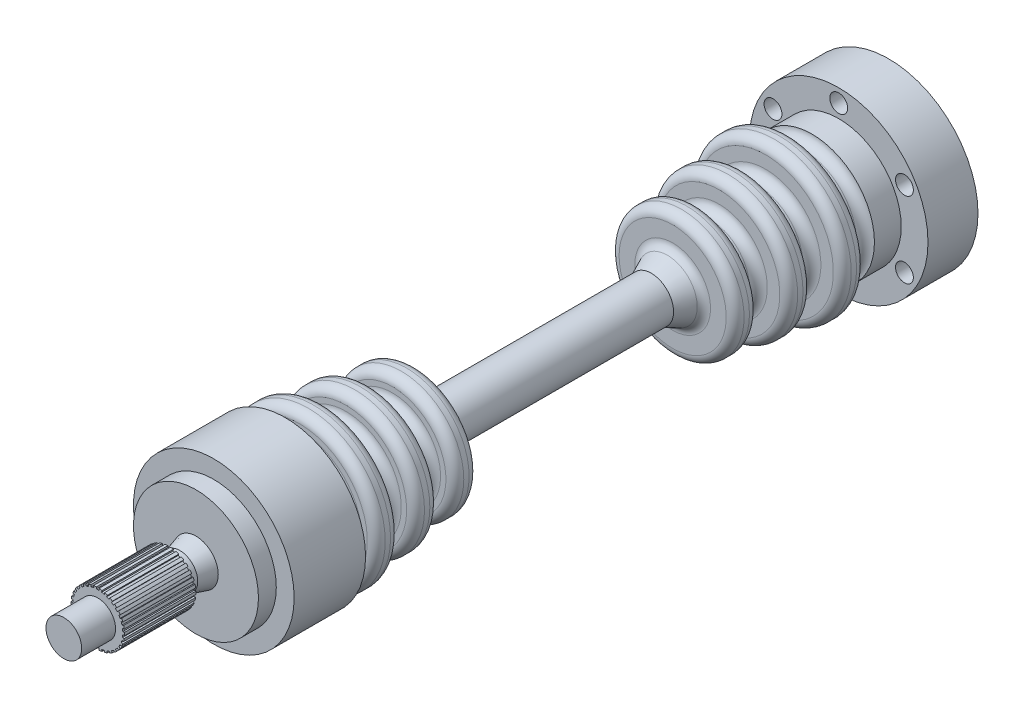
SolidWorks part; units mm, degrees
ref_plane "Płaszczyzna przednia" through (0, 0, 0) normal (0, 0, 1) x (1, 0, 0)
ref_plane "Płaszczyzna górna" through (0, 0, 0) normal (0, 1, 0) x (1, 0, 0)
ref_plane "Płaszczyzna prawa" through (0, 0, 0) normal (1, 0, 0) x (0, 0, -1)
sketch "Szkic1" plane through (0, 0, 0) normal (0, 0, 1) x (1, 0, 0)
  circle A1 centre (0, 0) radius 35
  dimension "D2" = 70
extrude "Dodanie-wyciągnięcie1" add sketch "Szkic1" along normal blind 10 contours A1
sketch "Szkic2" plane through (0, 0, 10) normal (0, 0, 1) x (1, 0, 0)
  circle A0 centre (0, 0) radius 50
  dimension "D1" = 100
extrude "Dodanie-wyciągnięcie2" add sketch "Szkic2" along normal blind 28
sketch "Szkic3" plane through (0, 0, 10) normal (0, 0, -1) x (-1, 0, 0)
  circle A0 centre (0, 42.5) radius 5
  dimension "D1" = 10
  dimension "D2" = 42.5
extrude "Wytnij-wyciągnięcie1" cut sketch "Szkic3" against normal through all
pattern_circular "Szyk kołowy1" count 6 over 360 about axis through (0, 0, 0) along (0, 0, 1) of "Wytnij-wyciągnięcie1"
sketch "Szkic6" plane through (0, 0, 38) normal (0, 0, 1) x (1, 0, 0)
  circle A0 centre (0, 0) radius 35
  dimension "D1" = 70
extrude "Dodanie-wyciągnięcie4" add sketch "Szkic6" along normal blind 15
sketch "Szkic4" plane through (0, 0, 0) normal (1, 0, 0) x (0, 0, -1)
  line L0 (-53, 30) -> (-66, 30)
  line L2 (-66, 30) -> (-66, 43)
  line L3 (-66, 43) -> (-79, 43)
  line L4 (-79, 43) -> (-79, 26)
  line L5 (-79, 26) -> (-92, 26)
  line L6 (-92, 26) -> (-92, 39)
  line L7 (-92, 39) -> (-105, 39)
  line L8 (-105, 39) -> (-105, 22)
  line L9 (-105, 22) -> (-118, 22)
  line L10 (-118, 22) -> (-118, 35)
  line L11 (-118, 35) -> (-131, 35)
  line L12 (-131, 35) -> (-131, 18)
  line L13 (-131, 18) -> (-143, 12.5)
  line L14 (-53, 35) -> (-53, -35) construction
  line L15 (-143, 12.5) -> (-143, 0)
  line L16 (-143, 0) -> (-53, 0)
  line L17 (-53, 0) -> (-53, 30)
  dimension "D1" = 12.5
  dimension "D2" = 13
  dimension "D3" = 13
  dimension "D4" = 90
  dimension "D5" = 4
  dimension "D6" = 4
  dimension "D7" = 4
  dimension "D8" = 4
  dimension "D9" = 4
  dimension "D10" = 13
  dimension "D11" = 30
revolve "Obrót1" add sketch "Szkic4" angle 360 about L16
fillet "Zaokrąglenie1" radius 5 13 edges at (39, 0, 105) (30, 0, 53) (30, 0, 66) (43, 0, 66) (43, 0, 79) (26, 0, 79) (26, 0, 92) (22, 0, 105) (18, 0, 131) (35, 0, 131) (35, 0, 118) (22, 0, 118) (39, 0, 92)
sketch "Szkic7" plane through (0, 0, 143) normal (0, 0, 1) x (1, 0, 0)
  circle A1 centre (0, 0) radius 12.5
  circle A2 centre (0, 0) radius 12.5
  dimension "D1" = 0
extrude "Dodanie-wyciągnięcie5" add sketch "Szkic7" along normal blind 120
ref_plane "Płaszczyzna1" through (0, 0, 203) normal (0, 0, 1) x (1, 0, 0)
mirror "Lustro1" about plane through (0, 0, 203) normal (0, 0, 1) of "Zaokrąglenie1", "Obrót1"
ref_plane "Płaszczyzna2" through (0, 0, 348) normal (0, 0, 1) x (1, 0, 0)
sketch "Szkic8" plane through (0, 0, 348) normal (0, 0, 1) x (1, 0, 0)
  circle A0 centre (0, 0) radius 45
  dimension "D1" = 90
extrude "Dodanie-wyciągnięcie6" add sketch "Szkic8" along normal blind 40 contours A0
sketch "Szkic10" plane through (0, 0, 388) normal (0, 0, 1) x (1, 0, 0)
  circle A0 centre (0, 0) radius 35
  dimension "D1" = 70
extrude "Dodanie-wyciągnięcie7" add sketch "Szkic10" along normal blind 10
sketch "Szkic9" plane through (0, 0, 0) normal (1, 0, 0) x (0, 0, -1)
  line L0 (-398, 12.5) -> (-407, 10)
  line L2 (-407, 10) -> (-413, 10)
  line L3 (-413, 10) -> (-413, 0)
  line L4 (-413, 0) -> (-398, 0)
  line L5 (-398, 0) -> (-398, 12.5)
  line L6 (-398, 35) -> (-398, -35) construction
  dimension "D1" = 12.5
  dimension "D2" = 15
  dimension "D3" = 6
  dimension "D4" = 10
revolve "Obrót2" add sketch "Szkic9" angle 360 about L4
sketch "Szkic11" plane through (0, 0, 413) normal (0, 0, 1) x (1, 0, 0)
  circle A0 centre (0, 0) radius 15
  dimension "D1" = 30
extrude "Dodanie-wyciągnięcie8" add sketch "Szkic11" along normal blind 40
sketch "Szkic12" plane through (0, 0, 453) normal (0, 0, 1) x (1, 0, 0)
  line L1 (-0.75, 16) -> (0.75, 16)
  line L2 (-0.75, 16) -> (-0.75, 14)
  line L3 (-0.75, 14) -> (0.75, 14)
  line L4 (0.75, 16) -> (0.75, 14)
  circle A0 centre (0, 0) radius 15 construction
  circle A1 centre (0, 0) radius 15
  point P7 (0, 16)
  dimension "D1" = 2
  dimension "D2" = 1.5
  dimension "D3" = 14
extrude "Wytnij-wyciągnięcie2" cut sketch "Szkic12" against normal up to next contours L2 L3 L4 L1
pattern_circular "Szyk kołowy2" count 30 over 360 about axis through (0, -0.0306, 0) along (0, 0, 1) of "Wytnij-wyciągnięcie2"
sketch "Szkic13" plane through (0, 0, 453) normal (0, 0, 1) x (1, 0, 0)
  circle A0 centre (0, 0) radius 10
  dimension "D1" = 20
extrude "Dodanie-wyciągnięcie9" add sketch "Szkic13" along normal blind 19
